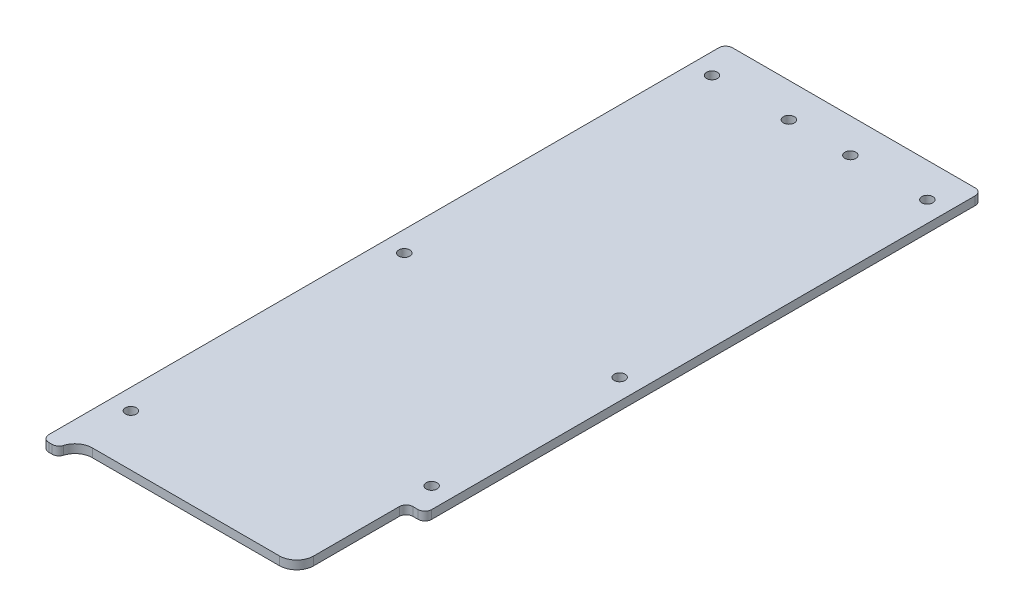
SolidWorks part; units mm, degrees
ref_plane "Front Plane" through (0, 0, 0) normal (0, 0, 1) x (1, 0, 0)
ref_plane "Top Plane" through (0, 0, 0) normal (0, 1, 0) x (1, 0, 0)
ref_plane "Right Plane" through (0, 0, 0) normal (1, 0, 0) x (0, 0, -1)
sketch "Sketch1" plane through (0, 0, 0) normal (0, 1, 0) x (1, 0, 0)
  line L0 (-39.9997, 0) -> (-39.9997, 114.3) construction
  line L1 (-47.625, 127) -> (47.625, 127)
  line L2 (-47.625, 127) -> (-47.625, -127)
  line L3 (-47.625, -127) -> (47.625, -127)
  line L4 (47.625, 127) -> (47.625, -127)
  line L5 (-47.625, 127) -> (47.625, -127) construction
  line L6 (-47.625, -127) -> (47.625, 127) construction
  line L7 (0, 0) -> (0, 127) construction
  line L8 (-39.9997, 0) -> (-39.9997, -101.6) construction
  line L9 (-39.9997, 0) -> (0, 0) construction
  line L10 (-41.275, -127) -> (-41.275, -120.65)
  line L11 (-41.275, -120.65) -> (41.275, -120.65)
  line L12 (41.275, -120.65) -> (41.275, -127)
  line L13 (-39.9997, 114.3) -> (-11.4247, 114.3) construction
  line L14 (39.9997, 114.3) -> (11.4247, 114.3) construction
  circle A0 centre (-39.9997, 114.3) radius 2.032
  circle A1 centre (-39.9997, 0) radius 2.032
  circle A2 centre (-39.9997, -101.6) radius 2.032
  circle A3 centre (39.9997, -101.6) radius 2.032
  circle A4 centre (39.9997, 0) radius 2.032
  circle A5 centre (39.9997, 114.3) radius 2.032
  circle A6 centre (-11.4247, 114.3) radius 2.032
  circle A7 centre (11.4247, 114.3) radius 2.032
  circle A8 centre (-39.9997, -69.85) radius 2.032
  circle A9 centre (39.9997, -69.85) radius 2.032
  point P0 (0, 0)
  dimension "D4" = 4.064
  dimension "D10" = 28.575
  dimension "D1" = 95.25
  dimension "D2" = 254
  dimension "D3" = 7.6253
  dimension "D5" = 12.7
  dimension "D6" = 25.4
  dimension "D7" = 6.35
  dimension "D8" = 6.35
  dimension "D9" = 6.35
  dimension "D11" = 69.85
extrude "Boss-Extrude1" add sketch "Sketch1" along normal blind 3.175 contours L4 L1 L2 L3 A4 A0 A1 A2 A3 A5 | A8 | A3 region at (0, 0, -2.6944) region at (39.9997, 0, 101.6) region at (-39.9997, 0, 69.85)
fillet "Fillet1" radius 2.54 4 edges at (-47.625, 1.5875, -127) (47.625, 1.5875, -127) (47.625, 1.5875, 127) (-47.625, 1.5875, 127)
fillet "Fillet2" radius 2.54 2 edges at (41.275, 1.5875, 127) (-41.275, 1.5875, 127)
fillet "Fillet3" radius 6.35 2 edges at (41.275, 1.5875, 120.65) (-41.275, 1.5875, 120.65)
sketch "Sketch2" plane through (0, 0, 0) normal (0, -1, 0) x (1, 0, 0)
  line L0 (41.91, 131.8831) -> (41.91, 109.8659) construction
  line L1 (41.91, 109.8659) -> (41.91, 106.3879) construction
  line L2 (41.91, 83.271) -> (41.91, 82.5325) construction
  line L3 (41.91, 82.5325) -> (41.91, 81.2514) construction
  line L4 (41.91, 83.271) -> (41.91, 106.3879) construction
  line L5 (41.91, 131.8831) -> (41.91, 109.8659)
  line L6 (41.91, 109.8659) -> (41.91, 106.3879)
  line L7 (41.91, 83.271) -> (41.91, 82.5325)
  line L8 (41.91, 82.5325) -> (41.91, 81.2514)
  line L9 (41.91, 83.271) -> (41.91, 106.3879)
  line L10 (41.91, 81.2514) -> (47.625, 81.2514)
  line L11 (47.625, -124.46) -> (47.625, 124.46) construction
  line L12 (41.91, 131.8831) -> (47.625, 131.8831)
  line L13 (47.625, 131.8831) -> (47.625, 81.2514)
  line L14 (40.64, 79.9814) -> (48.895, 79.9814)
  line L15 (48.895, 133.1531) -> (48.895, 79.9814)
  line L16 (40.64, 133.1531) -> (48.895, 133.1531)
  line L17 (40.64, 133.1531) -> (40.64, 109.8659)
  line L18 (40.64, 109.8659) -> (40.64, 106.3879)
  line L19 (40.64, 83.271) -> (40.64, 106.3879)
  line L20 (40.64, 83.271) -> (40.64, 82.5325)
  line L21 (40.64, 82.5325) -> (40.64, 79.9814)
  arc M7 (43.815, 127) -> (41.3809, 125.1857) centre (43.815, 124.46) ccw
  arc M8 (41.3809, 125.1857) -> (35.2956, 120.65) centre (35.2956, 127) cw
  line M18 (47.625, -124.46) -> (47.625, 124.46)
  dimension "D1" = 1.27
extrude "Cut-Extrude1" cut sketch "Sketch2" against normal through all contours L20 L21 L14 L10 L8 L7 L9 L19 M18 | L19 L9 L6 L5 L17 L18 M7 M8 | L13 L10 L8 L7 L9 L6 L5 L12 region at (41.6752, 0, 99.9787)
fillet "Fillet4" radius 6.35 1 edges at (40.64, 1.5875, 123.5708)
fillet "Fillet5" radius 2.54 2 edges at (47.625, 1.5875, 79.9814) (40.64, 1.5875, 79.9814)
